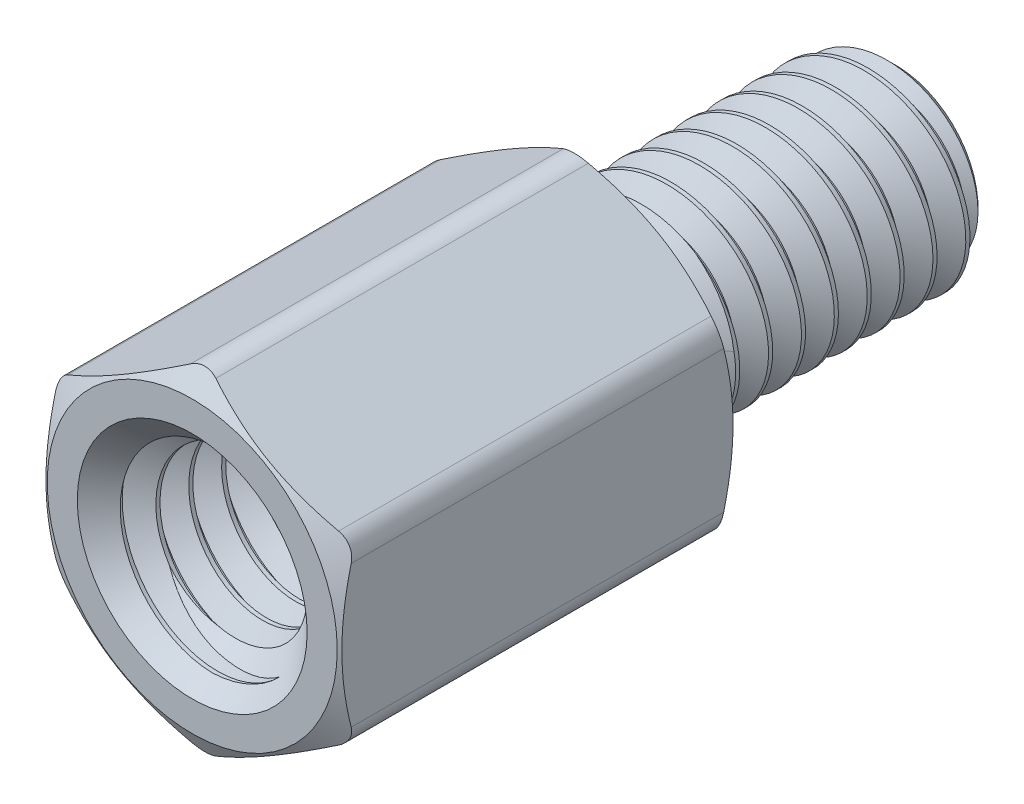
SolidWorks part; units mm, degrees
ref_plane "Front Plane" through (0, 0, 0) normal (0, 0, 1) x (1, 0, 0)
ref_plane "Top Plane" through (0, 0, 0) normal (0, 1, 0) x (1, 0, 0)
ref_plane "Right Plane" through (0, 0, 0) normal (1, 0, 0) x (0, 0, -1)
sketch "Sketch1" plane through (0, 0, 0) normal (0, 0, 1) x (1, 0, 0)
  line L1 (2.25, 1.299) -> (0, 2.5981)
  line L2 (0, 2.5981) -> (-2.25, 1.299)
  line L3 (-2.25, 1.299) -> (-2.25, -1.299)
  line L4 (-2.25, -1.299) -> (0, -2.5981)
  line L5 (0, -2.5981) -> (2.25, -1.299)
  line L6 (2.25, -1.299) -> (2.25, 1.299)
  circle A0 centre (0, 0) radius 2.25 construction
  point P10 (0, -2.25)
  dimension "Hex Size" = 4.5
sketch "Sketch2" plane through (0, 0, 0) normal (1, 0, 0) x (0, 0, -1)
  line L0 (4.7, 0) -> (-6, 0) construction
  line L2 (0, 1.5) -> (0, -1.5) construction
  line L3 (-3.2, 1.5) -> (-3.2, -1.5) construction
  line L4 (-6.4688, 1.5541) -> (-6.2188, 1.1211) construction
  line L5 (-6.2188, 1.1211) -> (-5.9688, 1.5541) construction
  line L6 (-5.9688, 1.5541) -> (-6.4688, 1.5541) construction
  line L7 (-6.4375, 1.5) -> (-6, 1.5) construction
  line L8 (-6.25, 1.1752) -> (-6.1875, 1.1752) construction
  line L9 (-6.2188, 1.1752) -> (-6.2188, 1.1211) construction
  line L10 (-6.2188, 1.5) -> (-6.2188, 1.5541) construction
  line L11 (4.6688, 1.5541) -> (5.1688, 1.5541) construction
  line L12 (5.1688, 1.5541) -> (4.9188, 1.1211) construction
  line L13 (4.9188, 1.1211) -> (4.6688, 1.5541) construction
  line L14 (4.7, 1.5) -> (5.1375, 1.5) construction
  line L15 (4.8875, 1.1752) -> (4.95, 1.1752) construction
  line L16 (4.9188, 1.1752) -> (4.9188, 1.1211) construction
  line L17 (4.9188, 1.5) -> (4.9188, 1.5541) construction
  line L18 (0, 2.5981) -> (-6, 2.5981) construction
  point P6 (0, 0)
  point P9 (-3.2, 0)
  dimension "Length" = 6
sketch "Sketch3" plane through (0, 0, 0) normal (1, 0, 0) x (0, 0, -1)
  line L0 (-3.2, 0) -> (4.7, 0)
  line L1 (-3.2, 1.5) -> (-3.2, -1.5) construction
  line L2 (4.7, 0) -> (4.7, 1.25)
  line L3 (4.7, 1.25) -> (4.45, 1.5)
  line L4 (4.45, 1.5) -> (0.7515, 1.5)
  line L5 (0.7515, 1.5) -> (0.564, 1.1752)
  line L6 (-3.2, 0) -> (-3.2, 1.25)
  line L7 (-3.2, 1.25) -> (-3.45, 1.5)
  line L8 (-3.45, 1.5) -> (-5.75, 1.5)
  line L9 (-5.75, 1.5) -> (-6, 1.75)
  line L10 (4.45, 0) -> (4.45, -1.5) construction
  line L11 (-6, 1.75) -> (-6, 2.25)
  line L12 (-6, 2.25) -> (0, 2.25)
  line L14 (0.564, 1.1752) -> (0.25, 1.1752)
  line L15 (0, 1.4252) -> (0, 2.25)
  arc A0 (0, 1.4252) -> (0.25, 1.1752) centre (0.25, 1.4252) ccw
  point P5 (-6, -2.25)
  point P8 (-4.75, -1.5)
  point P9 (3.45, -1.5)
  point P27 (0, 1.1752)
  dimension "D4" = 0.25
  dimension "D2" = 0.25
  dimension "D1" = 45
  dimension "D6" = 1.25
  dimension "D7" = 60
  dimension "D3" = 1.25
  dimension "D5" = 0.564
revolve "Revolve1" add sketch "Sketch3" angle 360 about L0 region at (0, 1.055, 0.2943)
sketch "Sketch4" plane through (0, 0, 6) normal (0, 0, 1) x (1, 0, 0)
  line L0 (0, 2.25) -> (0, 1.5) construction
  line L1 (-2.25, 1.299) -> (-2.25, -1.299)
  line L2 (-2.25, -1.299) -> (0, -2.5981)
  line L3 (0, -2.5981) -> (2.25, -1.299)
  line L4 (2.25, -1.299) -> (2.25, 1.299)
  line L5 (2.25, 1.299) -> (0, 2.5981)
  line L6 (0, 2.5981) -> (-2.25, 1.299)
  circle A0 centre (0, 0) radius 2.25 construction
  circle A1 centre (0, 0) radius 1.875
  circle A2 centre (0, 0) radius 2.25 construction
  point P16 (0, 1.875)
extrude "Boss-Extrude1" add sketch "Sketch4" against normal up to surface (6 mm away) up to face at (0, 2.25, 0)
sketch "Sketch5" plane through (0, 0, 6) normal (0, 0, 1) x (1, 0, 0)
  line L0 (-0.8604, 1.2287) -> (0.8604, -1.2287) construction
  line L1 (0, 1.5) -> (0, -1.5) construction
  line L3 (0, -2.7928) -> (0, 2.7928) construction
  circle A0 centre (0, 0) radius 2.205
  point P11 (0.8604, -1.2287)
  dimension "D1" = 4.41
  dimension "D2" = 35
extrude "Cut-Extrude1" cut sketch "Sketch5" against normal through all draft 60 flip side to cut
sketch "Sketch6" plane through (0, 0, 0) normal (0, 0, -1) x (-1, 0, 0)
  circle A0 centre (0, 0) radius 2.205
  circle A1 centre (0, 0) radius 2.205 construction
extrude "Cut-Extrude2" cut sketch "Sketch6" against normal through all draft 60 flip side to cut
fillet "Fillet1" radius 0.3825 6 edges at (0, 2.5981, 3) (-2.25, -1.299, 3) (0, -2.5981, 3) (2.25, -1.299, 3) (2.25, 1.299, 3) (-2.25, 1.299, 3)
sketch "Drawing1" plane through (0, 0, 0) normal (1, 0, 0) x (0, 0, -1)
  line L0 (-6, 1.5) -> (-3.2, 1.5) construction
  line L1 (-3.2, 1.5) -> (-3.2, -1.5) construction
  line L2 (-3.2, -1.5) -> (-6, -1.5) construction
sketch "Sketch7" plane through (0, 0, 0) normal (-1, 0, 0) x (0, 0, 1)
  line L0 (-4.8875, 1.1752) -> (-4.95, 1.1752)
  line L1 (-4.95, 1.1752) -> (-5.1531, 1.5271)
  line L2 (-5.1688, 1.5541) -> (-4.9188, 1.1211) construction
  line L3 (-5.1531, 1.5271) -> (-4.6844, 1.5271)
  line L4 (-4.9188, 1.1211) -> (-4.6688, 1.5541) construction
  line L5 (-4.6844, 1.5271) -> (-4.8875, 1.1752)
  line L6 (-4.9188, 1.5) -> (-4.9188, 1.5541) construction
  point P12 (-4.9188, 1.5271)
sketch "Sketch8" plane through (0, 0, -4.7) normal (0, 0, -1) x (-1, 0, 0)
  circle A0 centre (0, 0) radius 1.5
curve "Helix/Spiral1" pitch 0.5 height 4.559 radius 1.5 centre (0, 0, -4.7) axis (0, 0, 1) start towards (0, 1, 0)
sweep "Cut-Sweep1" cut profiles "Sketch7" path "Helix/Spiral1" align with end faces yes
sketch "Sketch9" plane through (0, 0, 3.2) normal (0, 0, 1) x (1, 0, 0)
  circle A0 centre (0, 0) radius 1.75
extrude "Boss-Extrude2" add sketch "Sketch9" along normal up to surface (2.8 mm away) up to face at (0, 1.75, 6)
sketch "Sketch10" plane through (0, 0, 0) normal (1, 0, 0) x (0, 0, -1)
  line L0 (4.7, 0) -> (-6, 0) construction
  line L1 (-3.2, 1.5) -> (-6, 1.5)
  line L2 (-3.2, 1.5) -> (-3.2, 0)
  line L3 (-3.2, 0) -> (-6, 0)
  line L4 (-6, 1.5) -> (-6, 0)
revolve "Revolve2" add sketch "Sketch10" angle 360 about L0
sketch "Sketch11" plane through (0, 0, 6) normal (0, 0, 1) x (1, 0, 0)
  circle A0 centre (0, 0) radius 1.5
  circle A1 centre (0, 0) radius 1.5 construction
sketch "Sketch12" plane through (0, 0, 0) normal (1, 0, 0) x (0, 0, -1)
  line L0 (-6.25, 1.1752) -> (-6.1875, 1.1752)
  line L1 (-6.1875, 1.1752) -> (-5.9844, 1.5271)
  line L2 (-6.2188, 1.1211) -> (-5.9688, 1.5541) construction
  line L3 (-5.9844, 1.5271) -> (-6.4531, 1.5271)
  line L4 (-6.4688, 1.5541) -> (-6.2188, 1.1211) construction
  line L5 (-6.4531, 1.5271) -> (-6.25, 1.1752)
  line L6 (-6.2188, 1.5) -> (-6.2188, 1.5541) construction
  point P12 (-6.2188, 1.5271)
curve "Helix/Spiral2" pitch 0.5 height 3.3 radius 1.5 centre (0, 0, 6) axis (0, 0, -1) start towards (0, 1, 0)
sweep "Cut-Sweep2" cut profiles "Sketch12" path "Helix/Spiral2" align with end faces yes
combine bodies "Combine1" operation type subtract main body 113 bodies to subtract 114
sketch "Sketch13" plane through (0, 0, 6) normal (0, 0, 1) x (1, 0, 0)
  circle A0 centre (0, 0) radius 1.7475
  dimension "D1" = 3.495
extrude "Cut-Extrude3" cut sketch "Sketch13" against normal through all draft 45
equation "\"Thread Pitch (B)/8@Sketch2\" = \"Thread Pitch (B)@Sketch2\" / 8"
equation "\"Thread Pitch (A)/8@Sketch2\" = \"Thread Pitch (A)@Sketch2\" / 8"
equation "\"D1@Sketch5\"=\"Hex Size@Sketch1\" * .98"
equation "\"D1@Fillet1\"=\"Hex Size@Sketch1\" * .085"
equation "\"D2@Sketch3\"=\"Thread Pitch (A)@Sketch2\" * .5"
equation "\"D4@Sketch3\" = \"D2@Sketch3\""
equation "\"D6@Sketch3\" = \"Thread Pitch (A)@Sketch2\" * 2.5"
equation "\"D3@Helix/Spiral1\" = \"Thread Length (A)@Sketch2\" - \"D5@Sketch3\" * .25"
equation "\"D4@Helix/Spiral1\" = \"Thread Pitch (A)@Sketch2\""
equation "\"D3@Sketch3\" = \"Thread Pitch (B)@Sketch2\" * 2.5"
equation "\"D5@Sketch3\" = \"Thread Length (A)@Sketch2\" * .12"
equation "\"D3@Helix/Spiral2\" = \"Minimum Thread Length (B)@Sketch2\" + \"Thread Pitch (B)@Sketch2\""
equation "\"D4@Helix/Spiral2\" = \"Thread Pitch (B)@Sketch2\""
equation "\"D1@Sketch13\"=(\"Hex Size@Sketch1\"-\"Thread Size (A)@Sketch2\")*.33+\"Thread Size (A)@Sketch2\""
